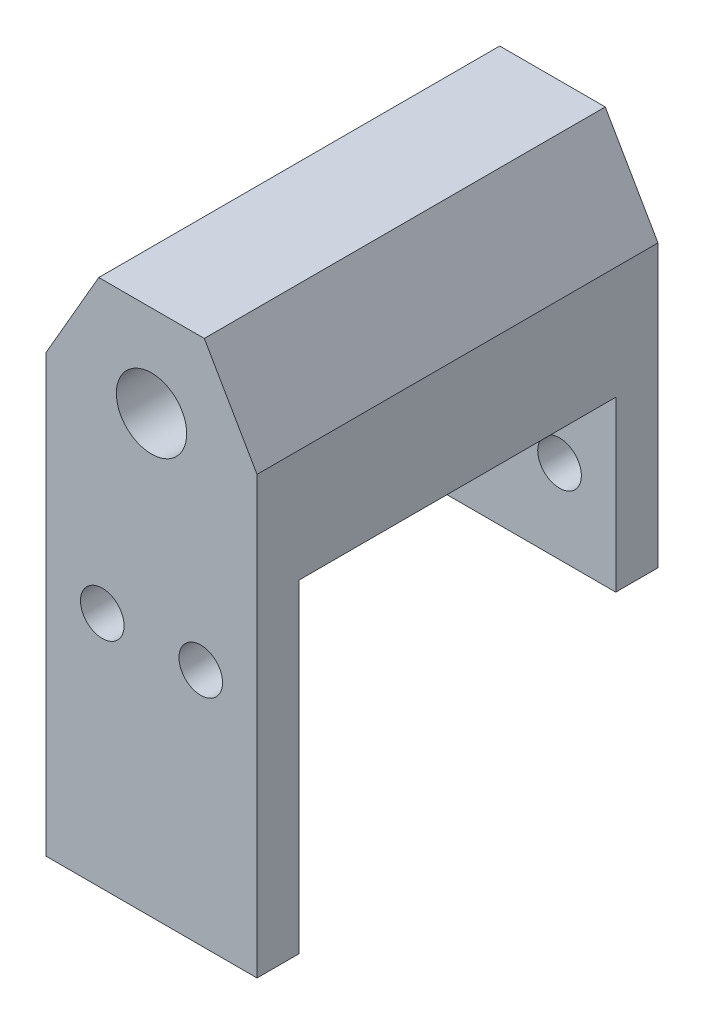
SolidWorks part; units mm, degrees
material "6061-T6 (SS)"
ref_plane "Front Plane" through (0, 0, 0) normal (0, 0, 1) x (1, 0, 0)
ref_plane "Top Plane" through (0, 0, 0) normal (0, 1, 0) x (1, 0, 0)
ref_plane "Right Plane" through (0, 0, 0) normal (1, 0, 0) x (0, 0, -1)
sketch "Sketch1" plane through (0, 0, 0) normal (0, 0, 1) x (1, 0, 0)
  line L0 (-7.5, 0) -> (-7.5, -8)
  line L1 (-7.5, -8) -> (7.5, -8)
  line L2 (7.5, -8) -> (7.5, 0)
  line L8 (7.5, 0) -> (3.75, 6.4952)
  line L9 (3.75, 6.4952) -> (-3.75, 6.4952)
  line L10 (-3.75, 6.4952) -> (-7.5, 0)
  line L11 (3.75, -6.4952) -> (7.5, 0) [skipped]
  line L12 (-3.75, -6.4952) -> (3.75, -6.4952) [skipped]
  line L13 (-7.5, 0) -> (-3.75, -6.4952) [skipped]
  circle A1 centre (0, 0) radius 3 construction
  circle A2 centre (0, 0) radius 6.4952 construction
  point P13 (0, -8)
  dimension "D1" = 6
  dimension "D2" = 15
  dimension "D4" = 8
extrude "Boss-Extrude1" add sketch "Sketch1" along normal blind 28.5
sketch "Sketch2" plane through (0, -8, 0) normal (0, -1, 0) x (1, 0, 0)
  line L0 (7.5, 28.5) -> (7.5, 0) construction
  line L1 (-7.5, 28.5) -> (7.5, 28.5)
  line L2 (-7.5, 28.5) -> (-7.5, 25.5)
  line L3 (-7.5, 25.5) -> (7.5, 25.5)
  line L4 (7.5, 28.5) -> (7.5, 25.5)
  line L5 (-7.5, 28.5) -> (-7.5, 0) construction
  line L6 (7.5, 0) -> (-7.5, 0)
  line L7 (7.5, 0) -> (7.5, 3)
  line L8 (7.5, 3) -> (-7.5, 3)
  line L9 (-7.5, 0) -> (-7.5, 3)
  line M6 (-7.5, 0) -> (7.5, 0)
  line M7 (7.5, 0) -> (7.5, 28.5)
  line M8 (7.5, 28.5) -> (-7.5, 28.5)
  line M9 (-7.5, 28.5) -> (-7.5, 0)
  dimension "D1" = 3
extrude "Boss-Extrude2" add sketch "Sketch2" along normal blind 23 contours L3 M9 M7 M8 region at (0, -8, 27)
extrude "Boss-Extrude3" add sketch "Sketch2<3>" along normal blind 12 contours L8 M7 M9 M6 region at (0, -8, 1.5)
sketch "Sketch2<3>" plane through (0, -8, 0) normal (0, -1, 0) x (1, 0, 0) same geometry as "Sketch2"
sketch "Sketch5" plane through (0, 0, 0) normal (0, 0, -1) x (-1, 0, 0)
  line L0 (-3.5, -14.05) -> (3.5, -14.05) construction
  line L1 (0, -14.05) -> (0, -8) construction
  circle A0 centre (-3.5, -14.05) radius 1.55
  circle A1 centre (3.5, -14.05) radius 1.55
  dimension "D1" = 3.1
  dimension "D2" = 6.05
  dimension "D3" = 7
extrude "Cut-Extrude1" cut sketch "Sketch5" against normal through all
hole_wizard "M6 Tapped Hole1" positions "Sketch3" profile "Sketch4" tap size "M6" standard "AS"
sketch "Sketch3" plane through (0, 0, 0) normal (0, 0, -1) x (-1, 0, 0)
  point P0 (0, 0)
cosmetic thread "Hole Thread1" parameters "D1"=8, "D2"=6
sketch "Sketch4" plane through (0, 0, 0) normal (1, 0, 0) x (0, 1, 0)
  line L0 (0, 0) -> (0, 9.5022)
  line L1 (0, 9.5022) -> (2.5, 8)
  line L2 (2.5, 8) -> (2.5, 0)
  line L5 (2.5, 0) -> (0, 0)
  line L10 (0, 9.5022) -> (-2.5, 8) construction
  line L11 (0, -6.35) -> (0, 107.95) construction
  dimension "Tap Drill Dia." = 5
  dimension "Tap Drill Depth" = 8
  dimension "Drill Angle" = 118
hole_wizard "M6 Tapped Hole2" positions "Sketch7" profile "Sketch8" tap size "M6" standard "AS"
sketch "Sketch7" plane through (0, 0, 28.5) normal (0, 0, 1) x (1, 0, 0)
  point P0 (0, 0)
sketch "Sketch8" plane through (0, 0, 28.5) normal (1, 0, 0) x (0, -1, 0)
  line L0 (0, 0) -> (0, 7.5022)
  line L1 (0, 7.5022) -> (2.5, 6)
  line L2 (2.5, 6) -> (2.5, 0)
  line L5 (2.5, 0) -> (0, 0)
  line L10 (0, 7.5022) -> (-2.5, 6) construction
  line L11 (0, -6.35) -> (0, 107.95) construction
  dimension "Tap Drill Dia." = 5
  dimension "Tap Drill Depth" = 6
  dimension "Drill Angle" = 118
cosmetic thread "Hole Thread2" parameters "D1"=6, "D2"=6
sketch "Sketch6" plane through (0, 0, 0) normal (0, 0, -1) x (-1, 0, 0)
  circle A0 centre (0, 0) radius 2.5
  dimension "D1" = 5
extrude "Cut-Extrude2" cut sketch "Sketch6" against normal through all
